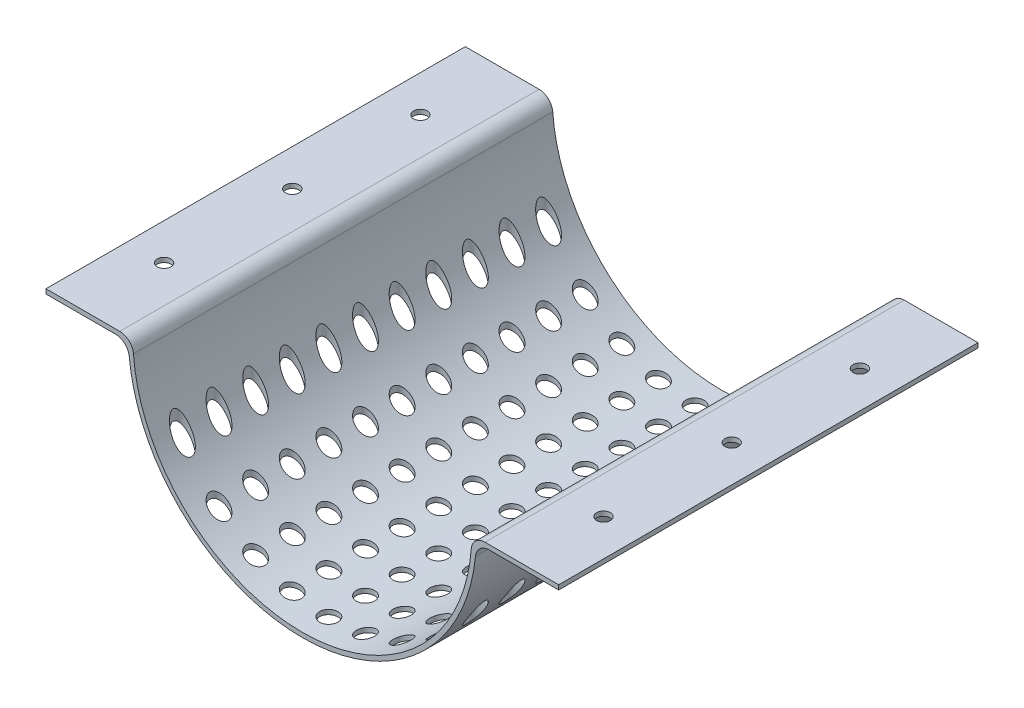
SolidWorks part; units mm, degrees
ref_plane "Front Plane" through (0, 0, 0) normal (0, 0, 1) x (1, 0, 0)
ref_plane "Top Plane" through (0, 0, 0) normal (0, 1, 0) x (1, 0, 0)
ref_plane "Right Plane" through (0, 0, 0) normal (1, 0, 0) x (0, 0, -1)
sketch "Sketch1" plane through (0, 0, 0) normal (0, 0, 1) x (1, 0, 0)
  line L0 (260.0247, 0) -> (-260.0247, 0) construction
  line L1 (0, -274.7223) -> (0, 274.7223) construction
  line L2 (126.6423, 0) -> (177.8, 0)
  line L3 (177.8, 0) -> (177.8, -3.175)
  line L4 (177.8, -3.175) -> (129.554, -3.175)
  line L5 (-177.8, -3.175) -> (-129.554, -3.175)
  line L6 (-177.8, 0) -> (-177.8, -3.175)
  line L7 (-126.6423, 0) -> (-177.8, 0)
  line L8 (127, -152.4711) -> (127, 152.4711) construction
  line L9 (-127, -154.3398) -> (-127, 154.3398) construction
  circle A0 centre (0, 0) radius 114.3 construction
  arc A1 (-117.1441, -8.8106) -> (117.1441, -8.8106) centre (0, 0) ccw
  arc A2 (-120.0744, -11.7707) -> (120.0744, -11.7707) centre (0, 0) ccw
  circle A3 centre (0, 0) radius 117.475 construction
  arc A4 (-129.554, -3.175) -> (-120.0744, -11.7707) centre (-129.554, -12.7) cw
  arc A5 (-120.65, 0) -> (120.65, 0) centre (0, 0) ccw construction
  arc A6 (129.554, -3.175) -> (120.0744, -11.7707) centre (129.554, -12.7) ccw
  arc A7 (-117.475, 0) -> (117.475, 0) centre (0, 0) ccw construction
  arc A8 (-117.1441, -8.8106) -> (-126.6423, 0) centre (-126.6423, -9.525) ccw
  arc A9 (117.1441, -8.8106) -> (126.6423, 0) centre (126.6423, -9.525) cw
  point P6 (0, 0)
  point P11 (120.65, 0)
  point P24 (127, 0)
  point P27 (-127, 0)
  point P29 (-120.6082, -3.175)
  point P32 (120.6082, -3.175)
  point P36 (-117.475, 0)
  point P38 (0, 0)
  dimension "D1" = 228.6
  dimension "D8" = 9.525
  dimension "D9" = 9.525
  dimension "D4" = 3.175
  dimension "D5" = 127
  dimension "D6" = 127
  dimension "D7" = 50.8
  dimension "D2" = 3.175
  dimension "D3" = 3.175
extrude "Boss-Extrude1" add sketch "Sketch1" along normal mid plane 290.83
sketch "Sketch2" plane through (0, 0, 0) normal (0, 1, 0) x (1, 0, 0)
  line L0 (-339.2719, 0) -> (339.2719, 0) construction
  line L1 (0, -268.1738) -> (0, 268.1738) construction
  circle A0 centre (0, 0) radius 6.35
  circle A1 centre (25.4, 0) radius 6.35
  circle A2 centre (50.8, 0) radius 6.35
  circle A3 centre (76.2, 0) radius 6.35
  circle A4 centre (101.6, 0) radius 6.35
  circle A5 centre (-50.8, 0) radius 6.35
  circle A6 centre (-101.6, 0) radius 6.35
  circle A7 centre (-76.2, 0) radius 6.35
  circle A8 centre (-25.4, 0) radius 6.35
  circle A9 centre (0, -25.4) radius 6.35
  circle A10 centre (25.4, -25.4) radius 6.35
  circle A11 centre (50.8, -25.4) radius 6.35
  circle A12 centre (76.2, -25.4) radius 6.35
  circle A13 centre (101.6, -25.4) radius 6.35
  circle A14 centre (-50.8, -25.4) radius 6.35
  circle A15 centre (-101.6, -25.4) radius 6.35
  circle A16 centre (-76.2, -25.4) radius 6.35
  circle A17 centre (-25.4, -25.4) radius 6.35
  circle A18 centre (0, -50.8) radius 6.35
  circle A19 centre (25.4, -50.8) radius 6.35
  circle A20 centre (50.8, -50.8) radius 6.35
  circle A21 centre (76.2, -50.8) radius 6.35
  circle A22 centre (101.6, -50.8) radius 6.35
  circle A23 centre (-50.8, -50.8) radius 6.35
  circle A24 centre (-101.6, -50.8) radius 6.35
  circle A25 centre (-76.2, -50.8) radius 6.35
  circle A26 centre (-25.4, -50.8) radius 6.35
  circle A27 centre (0, -76.2) radius 6.35
  circle A28 centre (25.4, -76.2) radius 6.35
  circle A29 centre (50.8, -76.2) radius 6.35
  circle A30 centre (76.2, -76.2) radius 6.35
  circle A31 centre (101.6, -76.2) radius 6.35
  circle A32 centre (-50.8, -76.2) radius 6.35
  circle A33 centre (-101.6, -76.2) radius 6.35
  circle A34 centre (-76.2, -76.2) radius 6.35
  circle A35 centre (-25.4, -76.2) radius 6.35
  circle A36 centre (0, -101.6) radius 6.35
  circle A37 centre (25.4, -101.6) radius 6.35
  circle A38 centre (50.8, -101.6) radius 6.35
  circle A39 centre (76.2, -101.6) radius 6.35
  circle A40 centre (101.6, -101.6) radius 6.35
  circle A41 centre (-50.8, -101.6) radius 6.35
  circle A42 centre (-101.6, -101.6) radius 6.35
  circle A43 centre (-76.2, -101.6) radius 6.35
  circle A44 centre (-25.4, -101.6) radius 6.35
  circle A45 centre (0, -127) radius 6.35
  circle A46 centre (25.4, -127) radius 6.35
  circle A47 centre (50.8, -127) radius 6.35
  circle A48 centre (76.2, -127) radius 6.35
  circle A49 centre (101.6, -127) radius 6.35
  circle A50 centre (-50.8, -127) radius 6.35
  circle A51 centre (-101.6, -127) radius 6.35
  circle A52 centre (-76.2, -127) radius 6.35
  circle A53 centre (-25.4, -127) radius 6.35
  circle A54 centre (-25.4, 127) radius 6.35
  circle A55 centre (-76.2, 127) radius 6.35
  circle A56 centre (-101.6, 127) radius 6.35
  circle A57 centre (-50.8, 127) radius 6.35
  circle A58 centre (101.6, 127) radius 6.35
  circle A59 centre (76.2, 127) radius 6.35
  circle A60 centre (50.8, 127) radius 6.35
  circle A61 centre (25.4, 127) radius 6.35
  circle A62 centre (0, 127) radius 6.35
  circle A63 centre (-25.4, 101.6) radius 6.35
  circle A64 centre (-76.2, 101.6) radius 6.35
  circle A65 centre (-101.6, 101.6) radius 6.35
  circle A66 centre (-50.8, 101.6) radius 6.35
  circle A67 centre (101.6, 101.6) radius 6.35
  circle A68 centre (76.2, 101.6) radius 6.35
  circle A69 centre (50.8, 101.6) radius 6.35
  circle A70 centre (25.4, 101.6) radius 6.35
  circle A71 centre (0, 101.6) radius 6.35
  circle A72 centre (-25.4, 76.2) radius 6.35
  circle A73 centre (-76.2, 76.2) radius 6.35
  circle A74 centre (-101.6, 76.2) radius 6.35
  circle A75 centre (-50.8, 76.2) radius 6.35
  circle A76 centre (101.6, 76.2) radius 6.35
  circle A77 centre (76.2, 76.2) radius 6.35
  circle A78 centre (50.8, 76.2) radius 6.35
  circle A79 centre (25.4, 76.2) radius 6.35
  circle A80 centre (0, 76.2) radius 6.35
  circle A81 centre (-25.4, 50.8) radius 6.35
  circle A82 centre (-76.2, 50.8) radius 6.35
  circle A83 centre (-101.6, 50.8) radius 6.35
  circle A84 centre (-50.8, 50.8) radius 6.35
  circle A85 centre (101.6, 50.8) radius 6.35
  circle A86 centre (76.2, 50.8) radius 6.35
  circle A87 centre (50.8, 50.8) radius 6.35
  circle A88 centre (25.4, 50.8) radius 6.35
  circle A89 centre (0, 50.8) radius 6.35
  circle A90 centre (-25.4, 25.4) radius 6.35
  circle A91 centre (-76.2, 25.4) radius 6.35
  circle A92 centre (-101.6, 25.4) radius 6.35
  circle A93 centre (-50.8, 25.4) radius 6.35
  circle A94 centre (101.6, 25.4) radius 6.35
  circle A95 centre (76.2, 25.4) radius 6.35
  circle A96 centre (50.8, 25.4) radius 6.35
  circle A97 centre (25.4, 25.4) radius 6.35
  circle A98 centre (0, 25.4) radius 6.35
  point P4 (0, 0)
  point P8 (0, 0)
  point P28 (0, -25.4)
  point P29 (0, -25.4)
  point P48 (0, -50.8)
  point P49 (0, -50.8)
  point P68 (0, -76.2)
  point P69 (0, -76.2)
  point P88 (0, -101.6)
  point P89 (0, -101.6)
  point P108 (0, -127)
  point P109 (0, -127)
  dimension "D1" = 12.7
  dimension "D2" = 5
  dimension "D3" = 6
extrude "Cut-Extrude1" cut sketch "Sketch2" against normal blind 304.8
sketch "Sketch3" plane through (0, 0, 0) normal (0, 1, 0) x (1, 0, 0)
  line L0 (-315.664, 0) -> (315.664, 0) construction
  line L1 (0, -212.5311) -> (0, 212.5311) construction
  line L2 (152.4, -206.7822) -> (152.4, 206.7822) construction
  line L3 (-152.4, -183.787) -> (-152.4, 183.787) construction
  line L4 (-270.7187, 152.4) -> (270.7187, 152.4) construction
  line L5 (-238.3162, -152.4) -> (238.3162, -152.4) construction
  circle A1 centre (152.4, 0) radius 4.7625
  circle A2 centre (152.4, 88.9) radius 4.7625
  circle A3 centre (152.4, -88.9) radius 4.7625
  circle A4 centre (-152.4, -88.9) radius 4.7625
  circle A5 centre (-152.4, 0) radius 4.7625
  circle A6 centre (-152.4, 88.9) radius 4.7625
  point P5 (0, 0)
  point P9 (0, 0)
  point P12 (152.4, 0)
  point P15 (-152.4, 0)
  point P18 (0, 152.4)
  point P21 (0, -152.4)
  dimension "D5" = 9.525
  dimension "D1" = 152.4
  dimension "D2" = 152.4
  dimension "D3" = 152.4
  dimension "D4" = 152.4
  dimension "D6" = 2
  dimension "D7" = 2
extrude "Cut-Extrude2" cut sketch "Sketch3" against normal blind 76.2
